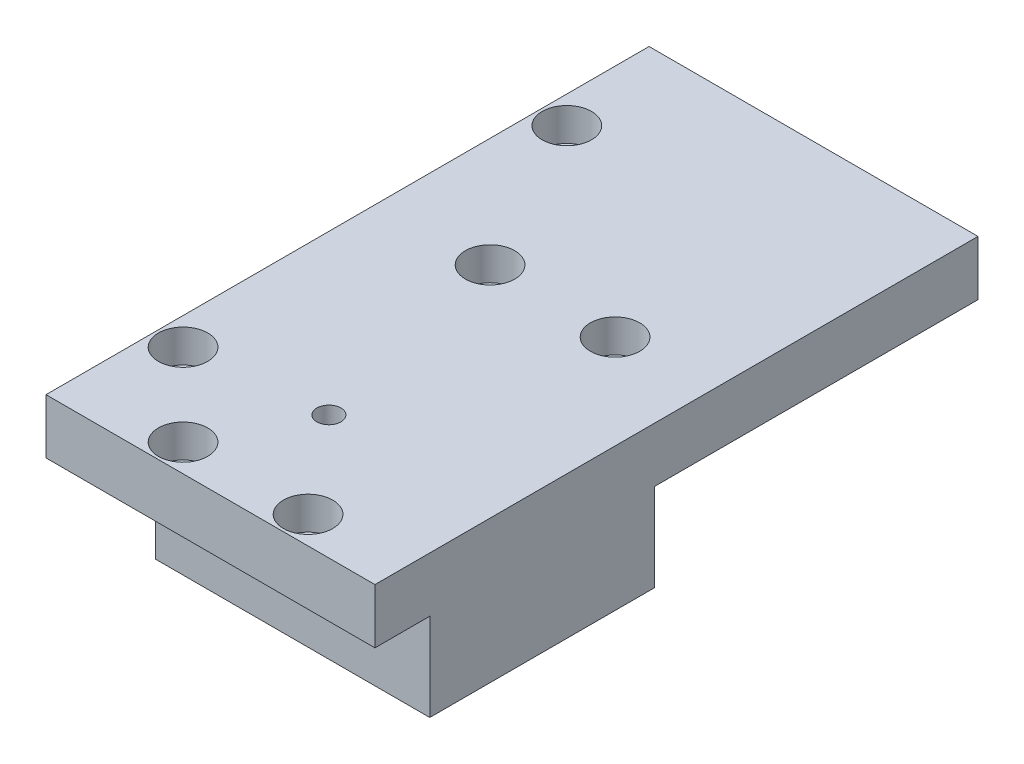
SolidWorks part; units mm, degrees
other "标注1"
sketch "草图3" plane through (0, 5, 29.5) normal (-0.6417, 0.7662, 0.0339) x (0.7661, 0.6384, 0.0747)
ref_plane "前视基准面" through (0, 0, 0) normal (0, 0, 1) x (1, 0, 0)
ref_plane "上视基准面" through (0, 0, 0) normal (0, 1, 0) x (1, 0, 0)
ref_plane "右视基准面" through (0, 0, 0) normal (1, 0, 0) x (0, 0, -1)
other "Configuration Table"
sketch "草图1" plane through (0, 0, 0) normal (0, 1, 0) x (1, 0, 0)
  line L33 (-30, -55) -> (0, -55)
  line L34 (-30, -55) -> (-30, 0)
  line L36 (0, -55) -> (0, 0)
  line L37 (-30, 0) -> (0, 0)
  dimension "D1" = 30
  dimension "D2" = 55
extrude "凸台-拉伸1" add sketch "草图1" along normal blind 5 contours L34 | L36 L37 L34 L33
sketch "草图4" plane through (0, 5, 0) normal (0, 1, 0) x (1, 0, 0)
  circle A0 centre (-27.5, -10) radius 2.25
  circle A1 centre (-27.5, -10) radius 1.5
  circle A2 centre (-27.5, -45) radius 2.25
  circle A3 centre (-27.5, -45) radius 1.5
  circle A4 centre (-20, -52.5) radius 2.25
  circle A5 centre (-20, -52.5) radius 1.5
  circle A6 centre (-8.6, -52.5) radius 2.25
  circle A7 centre (-8.6, -52.5) radius 1.5
  circle A8 centre (-8.6, -24.5) radius 2.25
  circle A9 centre (-8.6, -24.5) radius 1.5
  circle A10 centre (-39.5902, 20.3993) radius 2.25
  circle A11 centre (-39.5902, 20.3993) radius 1.5
  circle A12 centre (-20, -24.5) radius 2.25
  circle A13 centre (-20, -24.5) radius 1.5
  dimension "D1" = 3
  dimension "D2" = 4.5
extrude "切除-拉伸1" cut sketch "草图4" against normal through all contours A1 | A3 | A5 | A7 | A13 | A9
extrude "切除-拉伸2" cut sketch "草图4<3>" against normal offset from surface (3 mm away) 2 contours A0 | A2 | A4 | A6 | A12 | A8 up to face at (-27.5, 0, 11.5)
sketch "草图4<3>" plane through (0, 5, 0) normal (0, 1, 0) x (1, 0, 0) same geometry as "草图4"
sketch "草图5" plane through (0, 0, 0) normal (0, -1, 0) x (1, 0, 0)
  line L0 (0, 55) -> (0, 0) construction
  line L1 (0, 50) -> (-25, 50)
  line L2 (0, 50) -> (0, 29.5)
  line L3 (0, 29.5) -> (-25, 29.5)
  line L4 (-25, 50) -> (-25, 29.5)
  line L11 (-30, 55) -> (0, 55) construction
  line L12 (-30, 55) -> (-30, 0) construction
  dimension "D1" = 5
  dimension "D2" = 5
  dimension "D3" = 20.5
extrude "凸台-拉伸2" add sketch "草图5" along normal blind 8
sketch "草图6" plane through (0, -8, 0) normal (0, -1, 0) x (1, 0, 0)
  circle A0 centre (-4.6, 40.0359) radius 3.1
  circle A1 centre (-15.5, 43.702) radius 1.1
  dimension "D1" = 2.2
  dimension "D2" = 6.2
extrude "切除-拉伸3" cut sketch "草图6" against normal blind 2.6 contours A0
extrude "切除-拉伸4" cut sketch "草图6<3>" against normal through all contours A1
sketch "草图6<3>" plane through (0, -8, 0) normal (0, -1, 0) x (1, 0, 0) same geometry as "草图6"
